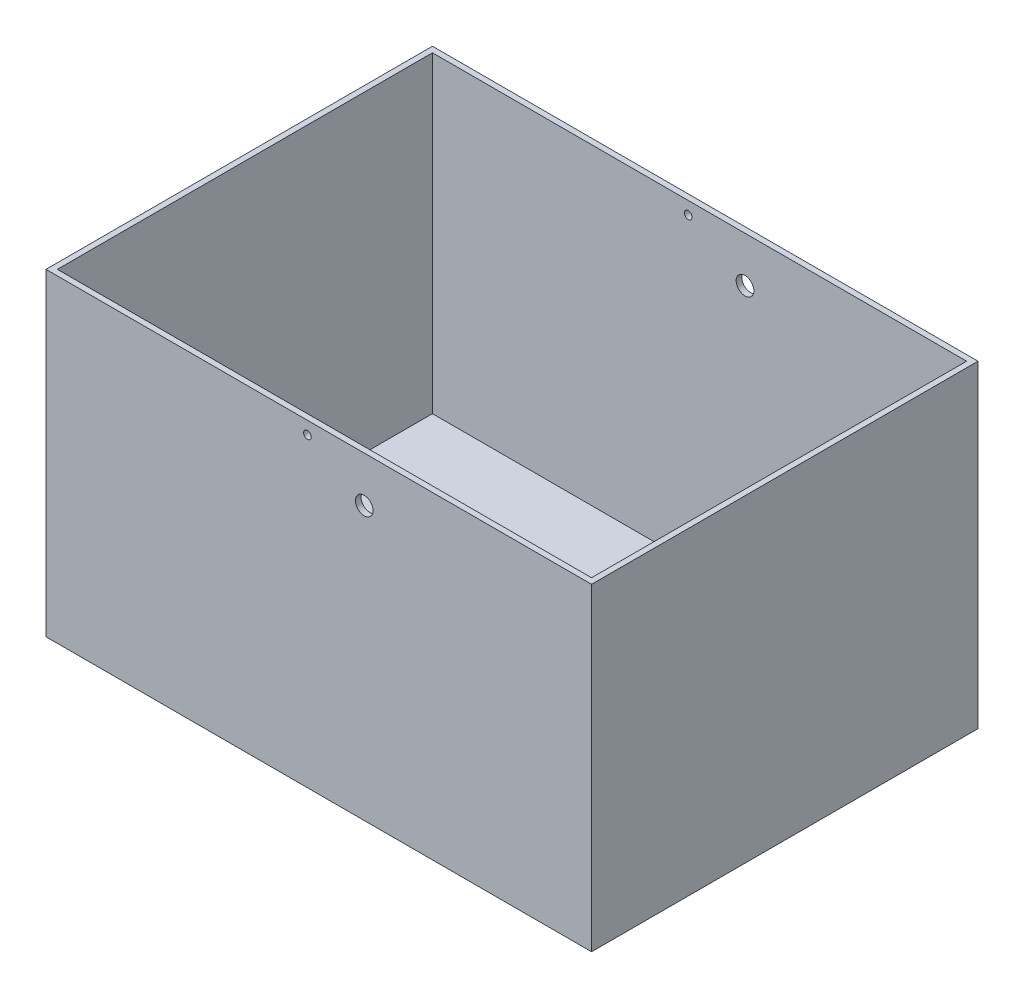
SolidWorks part; units mm, degrees
ref_plane "Front Plane" through (0, 0, 0) normal (0, 0, 1) x (1, 0, 0)
ref_plane "Top Plane" through (0, 0, 0) normal (0, 1, 0) x (1, 0, 0)
ref_plane "Right Plane" through (0, 0, 0) normal (1, 0, 0) x (0, 0, -1)
sketch "Sketch1" plane through (0, 0, 0) normal (0, 1, 0) x (1, 0, 0)
  line L0 (-149.225, 107.95) -> (-149.225, 104.775) construction
  line L1 (-152.4, 107.95) -> (152.4, 107.95)
  line L2 (-152.4, 107.95) -> (-152.4, -107.95)
  line L3 (-152.4, -107.95) -> (152.4, -107.95)
  line L4 (152.4, 107.95) -> (152.4, -107.95)
  line L5 (-152.4, 107.95) -> (152.4, -107.95) construction
  line L6 (-152.4, -107.95) -> (152.4, 107.95) construction
  line L7 (-149.225, -104.775) -> (149.225, -104.775)
  line L8 (-149.225, -104.775) -> (-149.225, 104.775)
  line L9 (-149.225, 104.775) -> (149.225, 104.775)
  line L10 (149.225, -104.775) -> (149.225, 104.775)
  line L11 (-149.225, -104.775) -> (149.225, 104.775) construction
  line L12 (-149.225, 104.775) -> (149.225, -104.775) construction
  line L13 (-149.225, 104.775) -> (-152.4, 104.775) construction
  point P0 (0, 0)
  point P6 (0, 0)
  dimension "D1" = 304.8
  dimension "D2" = 215.9
  dimension "D3" = 3.175
extrude "Boss-Extrude1" add sketch "Sketch1" along normal blind 3.175 contours L7 L10 L9 L8 region at (0, 0, 0)
extrude "Boss-Extrude2" add sketch "Sketch1<3>" along normal blind 177.8
sketch "Sketch1<3>" plane through (0, 0, 0) normal (0, 1, 0) x (1, 0, 0) same geometry as "Sketch1"
sketch "Sketch2" plane through (0, 0, 107.95) normal (0, 0, 1) x (1, 0, 0)
  line L0 (25.4, 152.4) -> (152.4, 152.4) construction
  line L1 (152.4, 177.8) -> (152.4, 0) construction
  line L2 (25.4, 152.4) -> (25.4, 177.8) construction
  line L3 (-152.4, 177.8) -> (152.4, 177.8) construction
  circle A0 centre (25.4, 152.4) radius 4.953
  circle A2 centre (-6.35, 170.7322) radius 2.15
  point P12 (0, 0)
  point P13 (0, 0)
  dimension "D1" = 9.906
  dimension "D4" = 4.3
  dimension "D2" = 25.4
  dimension "D3" = 127
  dimension "D5" = 18.3322
  dimension "D7" = 31.75
extrude "Cut-Extrude1" cut sketch "Sketch2" against normal through all both and the other way through all
